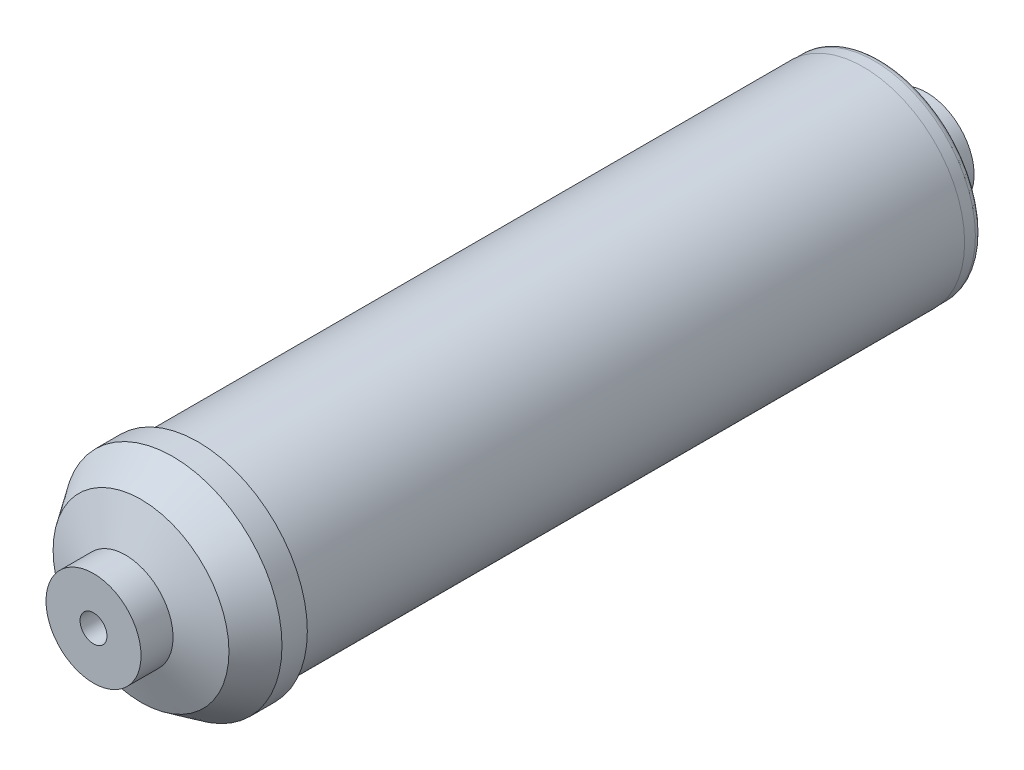
SolidWorks part; units mm, degrees
ref_plane "Front" through (0, 0, 0) normal (0, 0, 1) x (1, 0, 0)
ref_plane "Top" through (0, 0, 0) normal (0, 1, 0) x (1, 0, 0)
ref_plane "Right" through (0, 0, 0) normal (1, 0, 0) x (0, 0, -1)
sketch "Sketch1" plane through (0, 0, 0) normal (0, 0, 1) x (1, 0, 0)
  circle A0 centre (0, 0) radius 32
  dimension "D1" = 64
extrude "Boss-Extrude1" add sketch "Sketch1" along normal blind 210
sketch "Sketch2" plane through (0, 0, 210) normal (0, 0, 1) x (1, 0, 0)
  circle A0 centre (0, 0) radius 34.5
  dimension "D1" = 69
extrude "Boss-Extrude2" add sketch "Sketch2" along normal blind 18
chamfer "Chamfer1" distance 10 angle 34 1 edges at (34.5, 0, 228) first distance on face at (34.5, 0, 228)
sketch "Sketch3" plane through (0, 0, 228) normal (0, 0, 1) x (1, 0, 0)
  circle A0 centre (0, 0) radius 27.7549
extrude "Boss-Extrude3" add sketch "Sketch3" along normal blind 5
sketch "Sketch4" plane through (0, 0, 233) normal (0, 0, 1) x (1, 0, 0)
  circle A0 centre (0, 0) radius 15
  dimension "D1" = 30
extrude "Boss-Extrude4" add sketch "Sketch4" along normal blind 10
sketch "Sketch5" plane through (0, 0, 243) normal (0, 0, 1) x (1, 0, 0)
  circle A0 centre (0, 0) radius 4.25
  dimension "D1" = 8.5
extrude "Cut-Extrude1" cut sketch "Sketch5" against normal blind 854
chamfer "Chamfer2" distance 5 angle 69 1 edges at (27.7549, 0, 233) first distance on face at (27.7549, 0, 233)
sketch "Sketch7" plane through (0, 0, 0) normal (0, 0, -1) x (-1, 0, 0)
  circle A2 centre (0, 0) radius 31.9
  circle A3 centre (0, 0) radius 31.9
  dimension "D1" = 0.1
extrude "Boss-Extrude7" add sketch "Sketch7" along normal blind 10
chamfer "Chamfer3" distance 5 angle 74 1 edges at (-31.9, 0, -10) first distance on face at (-31.9, 0, -10)
fillet "Fillet1" radius 2 1 edges at (-31.9, 0, -5)
sketch "Sketch8" plane through (0, 0, -10) normal (0, 0, -1) x (-1, 0, 0)
  circle A0 centre (0, 0) radius 15
  dimension "D1" = 30
extrude "Boss-Extrude8" add sketch "Sketch8" along normal blind 10
sketch "Sketch9" plane through (0, 0, -20) normal (0, 0, -1) x (-1, 0, 0)
  circle A0 centre (0, 0) radius 4.25
  dimension "D1" = 8.5
extrude "Cut-Extrude2" cut sketch "Sketch9" against normal blind 311
